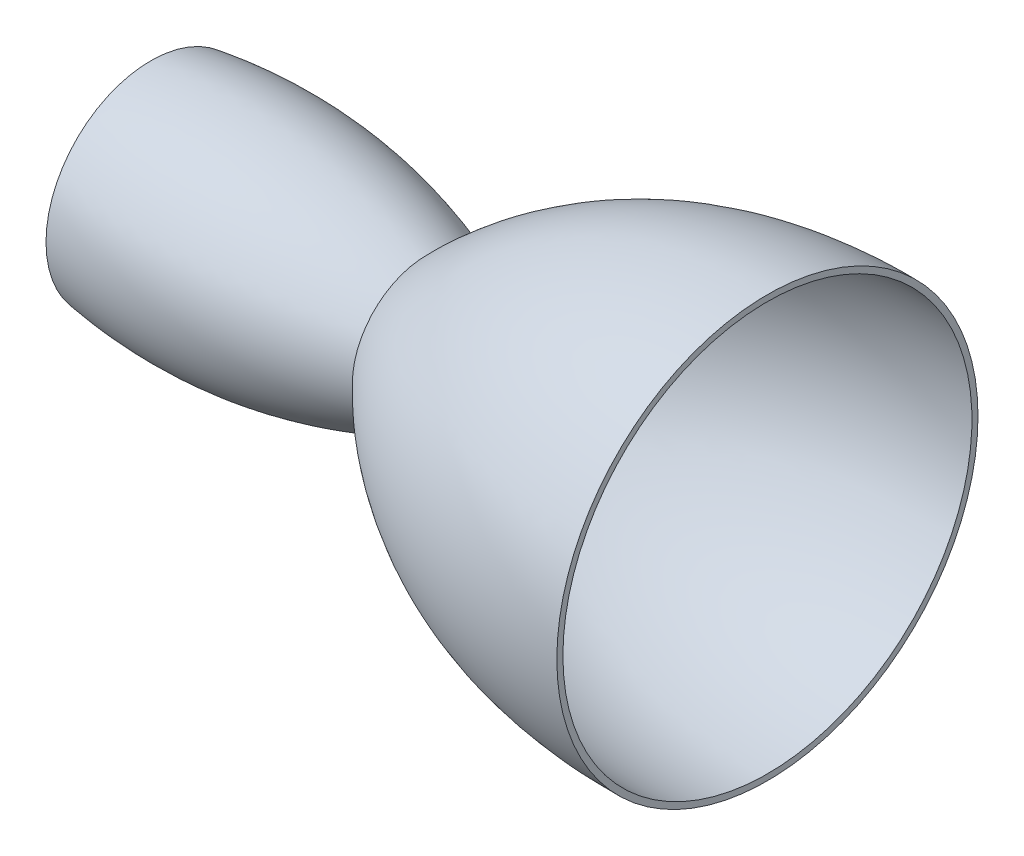
SolidWorks part; units mm, degrees
material "A286 Iron Base Superalloy"
ref_plane "Front Plane" through (0, 0, 0) normal (0, 0, 1) x (1, 0, 0)
ref_plane "Top Plane" through (0, 0, 0) normal (0, 1, 0) x (1, 0, 0)
ref_plane "Right Plane" through (0, 0, 0) normal (1, 0, 0) x (0, 0, -1)
sketch "Sketch1" plane through (0, 0, 0) normal (0, 0, 1) x (1, 0, 0)
  line L0 (-1229.8282, 0) -> (1426.3964, 0) construction
  line L1 (0, -100) -> (0, 100) construction
  line L2 (0, 0) -> (500, 0) construction
  line L3 (500, -300) -> (500, 300) construction
  line L5 (500, 308.89) -> (500, 300)
  line L6 (0, -108.89) -> (0, -100)
  line L7 (500, -308.89) -> (500, -300)
  line L8 (-404.4968, -144.8099) -> (-404.4968, 144.8099) construction
  line L9 (-404.4968, 144.8099) -> (-404.4968, 153.6999)
  line L10 (-404.4968, -144.8099) -> (-404.4968, -153.6999)
  spline S0 degree 2 poles (0, 100) (195.6384, 302.9991) (500, 300) knots 0 0 0 1 1 1
  spline S1 degree 2 poles (0, -100) (195.6384, -302.9991) (500, -300) knots 0 0 0 1 1 1
  spline S2 degree 2 poles (0, -108.89) (195.6384, -311.8891) (500, -308.89) knots 0 0 0 1 1 1
  spline S3 degree 2 poles (0, -100) (195.6384, -302.9991) (500, -300) knots 0 0 0 1 1 1
  spline S4 degree 2 poles (0, 108.89) (195.6384, 311.8891) (500, 308.89) knots 0 0 0 1 1 1
  spline S5 degree 2 poles (0, 100) (-196.731, 176.1531) (-404.4968, 144.8099) knots 0 0 0 1 1 1
  spline S6 degree 2 poles (0, -100) (-196.731, -176.1531) (-404.4968, -144.8099) knots 0 0 0 1 1 1
  spline S7 degree 2 poles (0, -108.89) (-196.731, -185.0431) (-404.4968, -153.6999) knots 0 0 0 1 1 1
  spline S9 degree 2 poles (0, 108.89) (-196.731, 185.0431) (-404.4968, 153.6999) knots 0 0 0 1 1 1
  point P8 (0, 0)
  point P14 (500, 0)
  point P22 (-404.4968, 0)
  dimension "D4" = 8.89
  dimension "D1" = 200
  dimension "D2" = 500
  dimension "D3" = 600
  dimension "D5" = 8.89
  dimension "D6" = 8.89
revolve "Revolve3" add sketch "Sketch1" angle 360 about L0 region at (490.7169, 304.445, 0)
